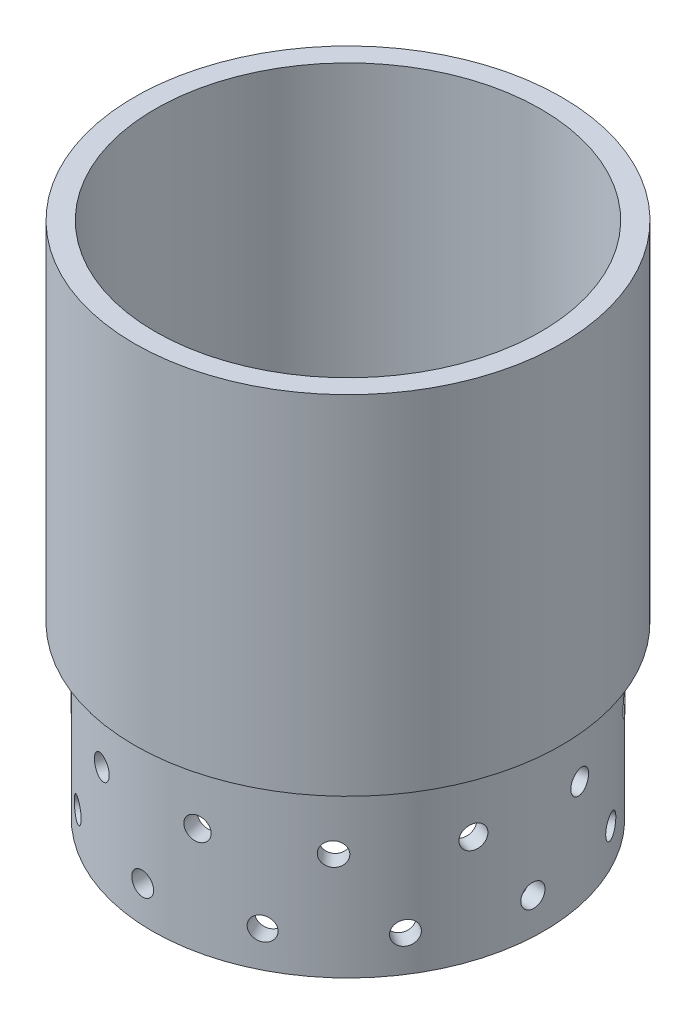
SolidWorks part; units mm, degrees
material "6061-T6 (SS)"
ref_plane "Front Plane" through (0, 0, 0) normal (0, 0, 1) x (1, 0, 0)
ref_plane "Top Plane" through (0, 0, 0) normal (0, 1, 0) x (1, 0, 0)
ref_plane "Right Plane" through (0, 0, 0) normal (1, 0, 0) x (0, 0, -1)
sketch "Sketch1" plane through (0, 0, 0) normal (0, 1, 0) x (1, 0, 0)
  circle A0 centre (0, 0) radius 69.596
  circle A1 centre (0, 0) radius 63.5
  dimension "D1" = 139.192
  dimension "D2" = 127
extrude "Boss-Extrude1" add sketch "Sketch1" along normal blind 57.15
ref_plane "Plane1" through (0, 0, 69.596) normal (0, 0, 1) x (1, 0, 0)
sketch "Sketch2" plane through (0, 0, 69.596) normal (0, 0, 1) x (1, 0, 0)
  circle A0 centre (0, 19.05) radius 3.2639
  dimension "D1" = 6.5278
  dimension "D2" = 19.05
extrude "Cut-Extrude1" [suppressed] cut sketch "Sketch2" against normal up to next
pattern_circular "CirPattern1" [suppressed] count 12 over 360 of bodies 102
ref_plane "Plane2" through (-21.5063, 0, 66.1897) normal (-0.309, 0, 0.9511) x (0, -1, 0)
sketch "Sketch3" plane through (-21.5063, 0, 66.1897) normal (-0.309, 0, 0.9511) x (0, -1, 0)
  line L1 (-57.15, 69.596) -> (-57.15, -69.596) construction
  circle A0 centre (-38.1, 0) radius 4.1021
  dimension "D2" = 8.2042
  dimension "D1" = 19.05
extrude "Cut-Extrude2" cut sketch "Sketch3" against normal up to next
pattern_circular "CirPattern2" count 12 over 360 about axis through (0, 57.15, 0) along (0, -1, 0) of "Cut-Extrude2"
sketch "Sketch4" plane through (0, 57.15, 0) normal (0, 1, 0) x (1, 0, 0)
  circle A0 centre (0, 0) radius 63.5 construction
  circle A1 centre (0, 0) radius 76.073
  circle A3 centre (0, 0) radius 63.5
  dimension "D1" = 152.146
extrude "Boss-Extrude2" [suppressed] add sketch "Sketch4" along normal blind 152.4
sketch "Sketch5" plane through (0, 57.15, 0) normal (0, 1, 0) x (1, 0, 0)
  circle A0 centre (0, 0) radius 63.5 construction
  circle A1 centre (0, 0) radius 63.5
  circle A2 centre (0, 0) radius 75.946
  dimension "D1" = 151.892
extrude "Boss-Extrude3" add sketch "Sketch5" along normal blind 127
other "Move Face1" flip direction yes face at (0, 57.15, 69.596) offset 3.302 parameters "D1"=3.302
ref_plane "Plane3" through (37.9047, 0, -58.3681) normal (0.5446, 0, -0.8387) x (0, -1, 0)
sketch "Sketch7" plane through (37.9047, 0, -58.3681) normal (0.5446, 0, -0.8387) x (0, -1, 0)
  line L0 (-60.452, 0) -> (0, 0) construction
  line L1 (-60.452, -75.946) -> (-60.452, 75.946) construction
  circle A0 centre (-12.827, 0) radius 4.1021
  dimension "D1" = 8.2042
  dimension "D2" = 47.625
extrude "Cut-Extrude3" cut sketch "Sketch7" against normal up to next
pattern_circular "CirPattern3" count 12 over 360 about axis through (0, 57.15, 0) along (0, -1, 0) of "Cut-Extrude3" reverse direction yes
sketch "Sketch8" plane through (0, 184.15, 0) normal (0, 1, 0) x (1, 0, 0)
  circle A0 centre (0, 0) radius 63.5 construction
  circle A1 centre (0, 0) radius 63.5
  circle A2 centre (0, 0) radius 68.58
  dimension "D1" = 5.08
extrude "Cut-Extrude4" cut sketch "Sketch8" against normal up to surface (123.698 mm away) up to face at (0, 60.452, 69.596)
fillet "Fillet1" radius 5.08 1 edges at (0, 60.452, 68.58)
